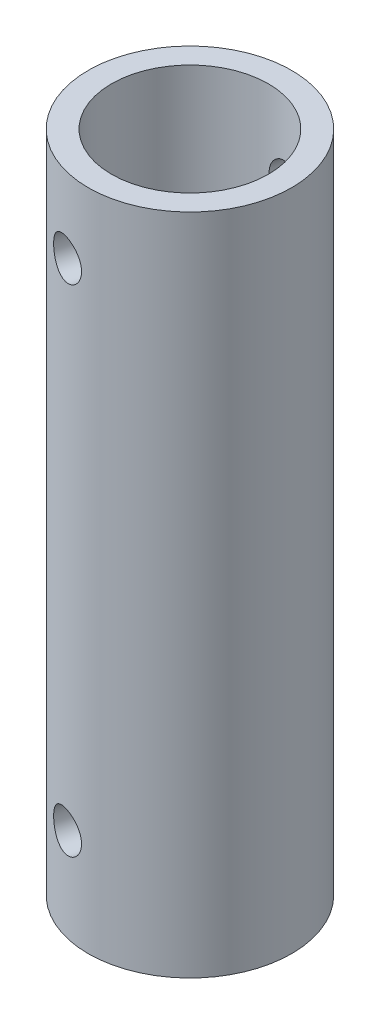
SolidWorks part; units mm, degrees
material "PVC Rigid"
ref_plane "Front Plane" through (0, 0, 0) normal (0, 0, 1) x (1, 0, 0)
ref_plane "Top Plane" through (0, 0, 0) normal (0, 1, 0) x (1, 0, 0)
ref_plane "Right Plane" through (0, 0, 0) normal (1, 0, 0) x (0, 0, -1)
sketch "Sketch2" plane through (0, 0, 0) normal (0, 1, 0) x (1, 0, 0)
  circle A0 centre (0, 0) radius 10.287
  circle A1 centre (0, 0) radius 13.335
  dimension "D1" = 20.574
  dimension "D2" = 26.67
extrude "Boss-Extrude2" add sketch "Sketch2" along normal blind 87
sketch "Sketch4" plane through (-1275.1015, -824.7099, -345.6043) normal (0.2616, 0, -0.9652) x (-0.9652, 0, -0.2616)
  circle A0 centre (-1321.1079, 901.7099) radius 2.6
  circle A1 centre (-1321.1079, 836.7099) radius 2.6
extrude "Cut-Extrude1" cut sketch "Sketch4" against normal blind 20 and the other way blind 20
